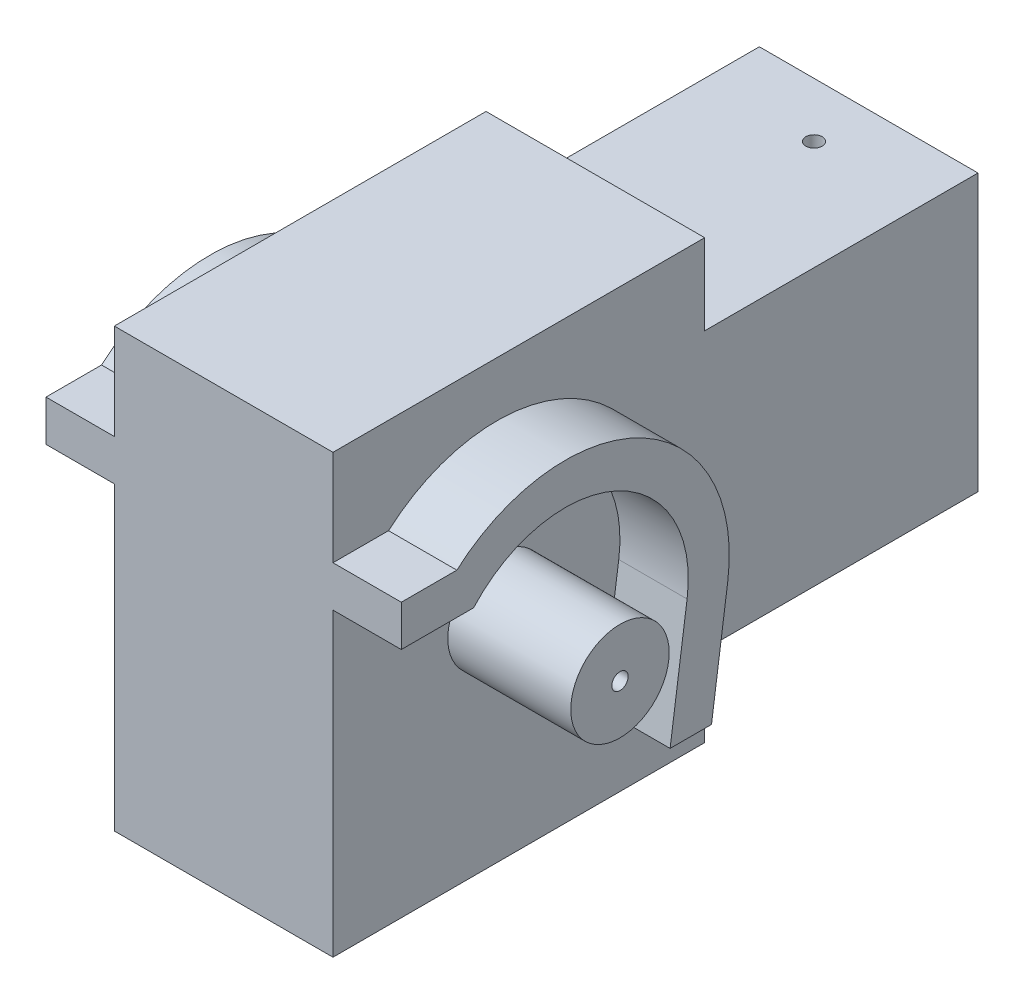
SolidWorks part; units mm, degrees
ref_plane "前视基准面" through (0, 0, 0) normal (0, 0, 1) x (1, 0, 0)
ref_plane "上视基准面" through (0, 0, 0) normal (0, 1, 0) x (1, 0, 0)
ref_plane "右视基准面" through (0, 0, 0) normal (1, 0, 0) x (0, 0, -1)
other "Configuration Table"
sketch "草图2" plane through (0, 0, 0) normal (1, 0, 0) x (0, 0, -1)
  line L0 (-6, 0) -> (17.6, 0) construction
  line L1 (-6, 8) -> (17.6, 8)
  line L2 (-6, 8) -> (-6, -8)
  line L3 (-6, -8) -> (17.6, -8)
  line L4 (17.6, 8) -> (17.6, -8)
  line L5 (1.8, 8) -> (1.8, -8)
  line L6 (4.4562, -0.6263) -> (3.4199, -8)
  line L7 (0, -4.5) -> (-6, -4.5)
  line L8 (0, -4.5) -> (0, 3)
  line L9 (0, 3) -> (-6, 3)
  line L10 (-6, -4.5) -> (-6, 3)
  line L12 (0, 4.5) -> (-6, 4.5)
  line L13 (4.9346, -8) -> (5.9416, -0.835)
  line L14 (0, 5) -> (17.6, 5)
  line L15 (0, 5) -> (0, -5)
  line L16 (0, -5) -> (17.6, -5)
  line L17 (17.6, 5) -> (17.6, -5)
  circle A0 centre (0, 0) radius 1.8
  circle A1 centre (0, 0) radius 4.5
  circle A2 centre (0, 0) radius 6
  dimension "D1" = 3.6
  dimension "D3" = 9
  dimension "D7" = 10
  dimension "D2" = 7.5
  dimension "D4" = 6
  dimension "D5" = 16
  dimension "D6" = 15.8
  dimension "D8" = 82
extrude "凸台-拉伸1" add sketch "草图2" along normal blind 4 contours L1 L4 L3 L2
extrude "凸台-拉伸3" add sketch "草图2<10>" along normal blind 4.5 from surface contours A0 L0 L8 | L8 L0 A0 | L0 L15 A0 | L0 A0 L15 region at (0, -0.7639, -0.7639) region at (0, 0.7639, -0.7639) region at (0, -0.7639, 0.7639) region at (0, 0.7639, 0.7639) starting at face at (4, 0, -5.8)
sketch "草图2<10>" plane through (0, 0, 0) normal (1, 0, 0) x (0, 0, -1) same geometry as "草图2"
sketch "草图5" plane through (8.5, 0, 0) normal (1, 0, 0) x (0, 0, -1)
  circle A0 centre (0, 0) radius 0.3
  dimension "D1" = 0.6
extrude "切除-拉伸10" cut sketch "草图5" against normal blind 1
extrude "凸台-拉伸2" add sketch "草图2<4>" along normal blind 2.5 from surface contours L12 A2 L9 A1 | L5 A2 L12 L15 L14 | A1 L5 L14 L15 | A1 L0 A2 L14 L5 | L14 A2 L5 | L0 A1 L6 A2 | A2 L6 L16 L13 | L16 L6 L3 L13 | A2 L12 L2 L9 region at (0, 2.6915, -4.1879) region at (0, -1.8211, -4.9358) region at (0, 4.6785, -0.9896) region at (0, 5.2074, 0.838) region at (0, 5.2565, -2.3339) region at (0, 3.8249, 3.3838) region at (0, -3.9797, -4.9725) region at (0, 3.8627, 5.2791) region at (0, -6.5, -4.3881) starting at face at (4, 0, -1.8)
sketch "草图2<4>" plane through (0, 0, 0) normal (1, 0, 0) x (0, 0, -1) same geometry as "草图2"
sketch "草图6" plane through (0, 0, -17.6) normal (0, 0, -1) x (-1, 0, 0)
  line L0 (-4, 6) -> (-4, -0.835) construction
  line L1 (0, 8) -> (-4, 8)
  line L2 (0, 8) -> (0, 5.05)
  line L3 (0, 5.05) -> (-4, 5.05)
  line L4 (-4, 8) -> (-4, 5.05)
  line L5 (-4, -0.835) -> (-4, -8) construction
  line L6 (0, -8) -> (-4, -8)
  line L7 (0, -8) -> (0, -5.05)
  line L8 (0, -5.05) -> (-4, -5.05)
  line L9 (-4, -8) -> (-4, -5.05)
  dimension "D1" = 10.1
extrude "切除-拉伸11" cut sketch "草图6" against normal blind 10
sketch "草图7" plane through (0, -5.05, 0) normal (0, -1, 0) x (1, 0, 0)
  line L0 (0, -7.6) -> (0, -17.6) construction
  line L4 (0, -17.6) -> (4, -17.6) construction
  line L5 (4, -7.6) -> (0, -7.6) construction
  circle A0 centre (0, -9.6) radius 0.3
  circle A1 centre (0, -15.6) radius 0.3
  dimension "D1" = 0.6
  dimension "D2" = 2
  dimension "D3" = 2
extrude "切除-拉伸12" cut sketch "草图7" against normal through all
sketch "草图8" plane through (6.5, 0, 0) normal (1, 0, 0) x (0, 0, -1)
  line L1 (7.6, -5.05) -> (-6, -5.05)
  line L2 (7.6, -5.05) -> (7.6, -8)
  line L3 (7.6, -8) -> (-6, -8)
  line L4 (-6, -5.05) -> (-6, -8)
extrude "切除-拉伸13" cut sketch "草图8" against normal up to surface (2.5 mm away) up to face at (4, 0, -1.8)
mirror "镜向1" about plane through (0, 0, 0) normal (1, 0, 0) of bodies 125 107
